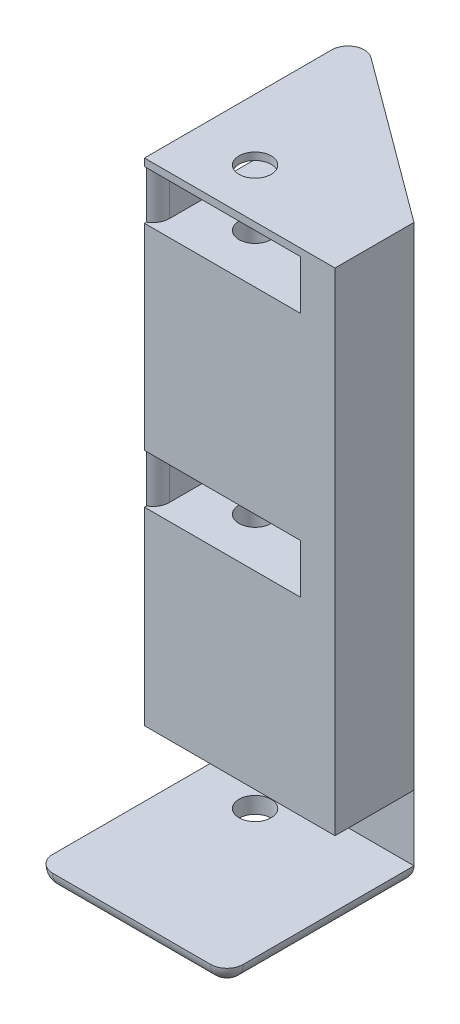
SolidWorks part; units mm, degrees
material "PLA/ABS"
ref_plane "Front Plane" through (0, 0, 0) normal (0, 0, 1) x (1, 0, 0)
ref_plane "Top Plane" through (0, 0, 0) normal (0, 1, 0) x (1, 0, 0)
ref_plane "Right Plane" through (0, 0, 0) normal (1, 0, 0) x (0, 0, -1)
other "Bounding Box"
ref_plane "Default Plane" through (-8.9266, -12.7485, 0) normal (-0.1736, 0.9848, 0) x (0.9848, 0.1736, 0)
sketch "Sketch1" plane through (0, 0, 0) normal (0, 1, 0) x (1, 0, 0)
  line B0 (-13.2357, 21.8055) -> (-13.2357, -16.2945)
  line B1 (-13.2357, -16.2945) -> (16.2964, -16.2945)
  line B2 (16.2964, -16.2945) -> (16.2964, 0)
  line B3 (16.2964, 0) -> (-13.2357, 21.8055)
  line B4 (16.2964, 0) -> (-13.2357, 0)
sketch_block_instance "Inter mount mount-1"
sketch_block "Inter mount mount" parameters "D1"=38.1
extrude "Boss-Extrude1" add sketch "Sketch1" along normal blind 6.35 contours B4 B3 B0 | B2 B4 B0 B1 region at (-3.3916, 0, -7.2685) region at (1.5304, 0, 8.1472)
extrude "Boss-Extrude2" add sketch "Sketch1<3>" against normal blind 82.55 contours B4 B3 B0 region at (-3.3916, 0, -7.2685)
sketch "Sketch1<3>" plane through (0, 0, 0) normal (0, 1, 0) x (1, 0, 0) same geometry as "Sketch1"
sketch "Sketch2" plane through (0, 0, 0) normal (0, -1, 0) x (-1, 0, 0)
  line L0 (13.2357, 0) -> (-16.2964, 0)
  line L5 (13.2357, 0) -> (13.2357, -16.2945)
  line L6 (-16.2964, 0) -> (-16.2964, -16.2945)
  line L7 (13.2357, -16.2945) -> (-16.2964, -16.2945)
  line L8 (13.2357, -16.2945) -> (-16.2964, -16.2945) construction
extrude "Cut-Extrude1" cut sketch "Sketch2" against normal blind 3.175
sketch "Sketch4" plane through (0, 6.35, 0) normal (0, 1, 0) x (1, 0, 0)
  line L0 (16.2964, -16.2945) -> (16.2964, 0) construction
  line L1 (-13.2357, -16.2945) -> (16.2964, -16.2945)
  line L2 (-13.2357, -16.2945) -> (-13.2357, -28.9945)
  line L3 (-13.2357, -28.9945) -> (16.2964, -28.9945)
  line L4 (16.2964, -16.2945) -> (16.2964, -28.9945)
  dimension "D1" = 12.7
extrude "Boss-Extrude3" add sketch "Sketch4" against normal up to surface (3.175 mm away) up to face at (1.5304, 3.175, 8.1472)
sketch3d "3DSketch1" plane through (0, 0, 0) normal (0, 0, 1) x (1, 0, 0)
  dimension "D1" = 3.175
sketch "Sketch7" plane through (3.8639, 0, -5.2331) normal (0.594, 0, -0.8045) x (-0.8045, 0, -0.594)
  line L0 (-13.11, -82.55) -> (-13.11, 3.175) construction
  line L1 (-13.11, -73.787) -> (23.6, -73.787)
  line L2 (-13.11, -73.787) -> (-13.11, -81.407)
  line L3 (-13.11, -81.407) -> (23.6, -81.407)
  line L4 (23.6, -73.787) -> (23.6, -81.407)
  line L5 (23.6, 6.35) -> (23.6, -82.55) construction
  line L6 (-13.11, -82.55) -> (23.6, -82.55) construction
  dimension "D1" = 1.143
  dimension "D2" = 7.62
extrude "Cut-Extrude4" cut sketch "Sketch7" against normal blind 13.589 contours L2 L1 L4 L3
sketch "Sketch8" plane through (3.8639, 0, -5.2331) normal (0.594, 0, -0.8045) x (-0.8045, 0, -0.594)
  line L0 (-13.11, -82.55) -> (-13.11, 3.175) construction
  line L1 (-13.11, -43.307) -> (23.6, -43.307)
  line L2 (-13.11, -43.307) -> (-13.11, -35.687)
  line L3 (-13.11, -35.687) -> (23.6, -35.687)
  line L4 (23.6, -43.307) -> (23.6, -35.687)
  line L5 (23.6, 6.35) -> (23.6, -82.55) construction
  line L7 (-8.81, -73.787) -> (9.5942, -73.787) construction
  dimension "D1" = 30.48
  dimension "D2" = 7.62
extrude "Cut-Extrude5" cut sketch "Sketch8" against normal blind 13.589
sketch "Sketch9" plane through (0, 0, 0) normal (0, 0, 1) x (1, 0, 0)
  line L1 (-13.2357, -82.55) -> (16.2964, -82.55)
  line L2 (-13.2357, -82.55) -> (-13.2357, 3.175)
  line L3 (-13.2357, 3.175) -> (16.2964, 3.175)
  line L4 (16.2964, -82.55) -> (16.2964, 3.175)
  line L5 (-11.9261, -43.307) -> (10.9513, -43.307)
  line L6 (-11.9261, -43.307) -> (-11.9261, -35.687)
  line L7 (-11.9261, -35.687) -> (10.9513, -35.687)
  line L8 (10.9513, -43.307) -> (10.9513, -35.687)
  line L9 (-11.9261, -81.407) -> (10.9513, -81.407)
  line L10 (-11.9261, -81.407) -> (-11.9261, -73.787)
  line L11 (-11.9261, -73.787) -> (10.9513, -73.787)
  line L12 (10.9513, -81.407) -> (10.9513, -73.787)
  line L13 (-13.2357, 3.175) -> (16.2964, 3.175)
  line L14 (-13.2357, 3.175) -> (-13.2357, -6.35)
  line L15 (-13.2357, -6.35) -> (16.2964, -6.35)
  line L16 (16.2964, 3.175) -> (16.2964, -6.35)
  line M9 (10.9513, -43.307) -> (-11.9261, -43.307)
  line M10 (-11.9261, -43.307) -> (-11.9261, -35.687)
  line M11 (-11.9261, -35.687) -> (10.9513, -35.687)
  line M12 (10.9513, -35.687) -> (10.9513, -43.307)
  line M13 (10.9513, -81.407) -> (-11.9261, -81.407)
  line M14 (-11.9261, -81.407) -> (-11.9261, -73.787)
  line M15 (-11.9261, -73.787) -> (10.9513, -73.787)
  line M16 (10.9513, -73.787) -> (10.9513, -81.407)
  line M17 (16.2964, -82.55) -> (16.2964, 3.175)
  line M20 (-13.2357, -82.55) -> (16.2964, -82.55)
  dimension "D1" = 9.525
extrude "Boss-Extrude5" add sketch "Sketch9" along normal blind 12.2428 contours L15 L2 M20 M17 M16 M13 M14 M15 M12 M9 M10 M11 region at (-12.4185, -44.45, 0)
sketch "Sketch10" plane through (0, -82.55, 0) normal (0, -1, 0) x (-1, 0, 0)
  line L0 (13.2357, 21.8055) -> (13.2357, -12.2428) construction
  line L1 (13.2357, -12.2428) -> (-16.2964, -12.2428) construction
  circle A0 centre (3.7107, -4.6228) radius 2.4892
  dimension "D1" = 4.9784
  dimension "D3" = 7.62
  dimension "D2" = 9.525
extrude "Cut-Extrude6" cut sketch "Sketch10" against normal through all both and the other way through all
fillet "Fillet2" radius 2.54 7 edges at (-13.2357, -38.1, -21.8055) (-11.9261, -77.597, 0) (-11.9261, -77.597, 12.2428) (-11.9261, -39.497, 12.2428) (-11.9261, -39.497, 0) (-13.2357, 4.7625, 28.9945) (16.2964, 4.7625, 28.9945)
fillet "Fillet3" radius 2.54 7 edges at (16.2964, 6.35, 13.2272) (15.5525, 6.35, 28.2505) (1.5304, 6.35, 28.9945) (-12.4917, 6.35, 28.2505) (-13.2357, 6.35, 4.8409) (-11.8401, 6.35, -19.0403) (3.5547, 6.35, -9.408)
mirror "Mirror1" about plane through (0, 6.35, 0) normal (0, 1, 0) of bodies 114
delete or keep bodies "Body-Delete/Keep 1" type delete bodies bodies 114
sketch "Sketch11" plane through (5.7498, 0, -7.7872) normal (0.594, 0, -0.8045) x (-0.8045, 0, -0.594)
  circle A0 centre (-11.0457, 24.13) radius 1.5875
  circle A1 centre (1.6543, 24.13) radius 1.5875
  circle A2 centre (14.3543, 24.13) radius 1.5875
  circle A3 centre (-11.0457, 49.53) radius 1.5875
  circle A4 centre (1.6543, 49.53) radius 1.5875
  circle A5 centre (14.3543, 49.53) radius 1.5875
  circle A6 centre (-11.0457, 74.93) radius 1.5875
  circle A7 centre (1.6543, 74.93) radius 1.5875
  circle A8 centre (14.3543, 74.93) radius 1.5875
  dimension "D1" = 3
  dimension "D2" = 3
extrude "Cut-Extrude7" cut sketch "Sketch11" against normal blind 6.35
sketch "Sketch12" plane through (-13.2357, 0, 0) normal (-1, 0, 0) x (0, 0, 1)
  line L1 (0, 9.525) -> (28.9945, 9.525)
  line L2 (0, 9.525) -> (0, 8.89)
  line L3 (0, 8.89) -> (28.9945, 8.89)
  line L4 (28.9945, 9.525) -> (28.9945, 8.89)
extrude "Cut-Extrude8" cut sketch "Sketch12" against normal through all both and the other way through all
